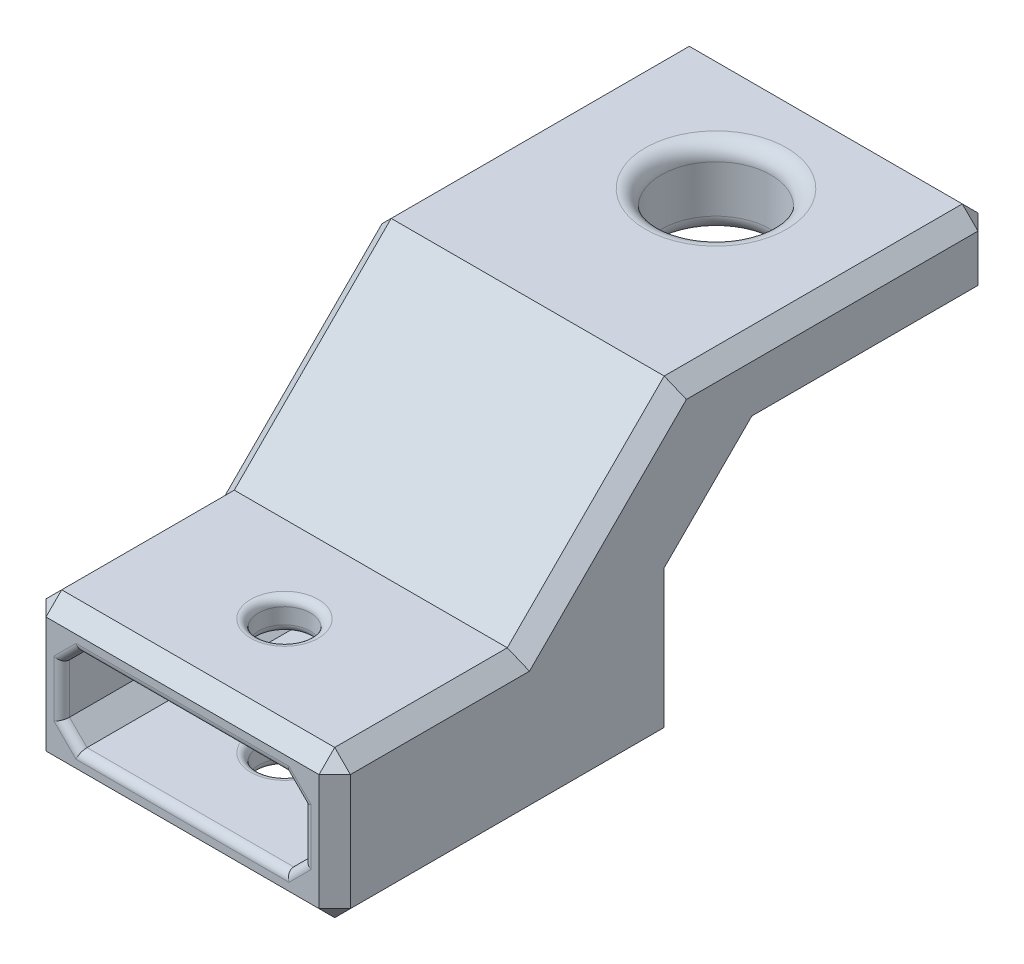
SolidWorks part; units mm, degrees
ref_plane "Plano frontal" through (0, 0, 0) normal (0, 0, 1) x (1, 0, 0)
ref_plane "Plano superior" through (0, 0, 0) normal (0, 1, 0) x (1, 0, 0)
ref_plane "Plano direito" through (0, 0, 0) normal (1, 0, 0) x (0, 0, -1)
sketch "Esboço1" plane through (0, 0, 0) normal (0, 0, 1) x (1, 0, 0)
  line L0 (15, 3) -> (14, 4) construction
  line L1 (15, 3) -> (15, 0) construction
  line L2 (14, -1) -> (15, 0) construction
  line L3 (14, -1) -> (1, -1) construction
  line L4 (0, 0) -> (1, -1) construction
  line L5 (0, 0) -> (0, 3) construction
  line L6 (1, 4) -> (0, 3) construction
  line L7 (1, 4) -> (14, 4) construction
sketch "Esboço2" plane through (0, 0, 0) normal (0, 0, 1) x (1, 0, 0)
  line L39 (-2.2, 6.2) -> (17.2, 6.2)
  line L40 (-2.2, 6.2) -> (-2.2, -3.2)
  line L41 (-2.2, -3.2) -> (17.2, -3.2)
  line L42 (17.2, 6.2) -> (17.2, -3.2)
  line L46 (15.2, 3.0828) -> (14.0828, 4.2)
  line L47 (15.2, -0.0828) -> (15.2, 3.0828)
  line L48 (14.0828, -1.2) -> (15.2, -0.0828)
  line L49 (0.9172, -1.2) -> (14.0828, -1.2)
  line L50 (-0.2, -0.0828) -> (0.9172, -1.2)
  line L51 (-0.2, 3.0828) -> (-0.2, -0.0828)
  line L52 (0.9172, 4.2) -> (-0.2, 3.0828)
  line L53 (14.0828, 4.2) -> (0.9172, 4.2)
  line L54 (15.2, 3.0828) -> (14.0828, 4.2)
  line L55 (15.2, -0.0828) -> (15.2, 3.0828)
  line L56 (14.0828, -1.2) -> (15.2, -0.0828)
  line L57 (0.9172, -1.2) -> (14.0828, -1.2)
  line L58 (-0.2, -0.0828) -> (0.9172, -1.2)
  line L59 (-0.2, 3.0828) -> (-0.2, -0.0828)
  line L60 (0.9172, 4.2) -> (-0.2, 3.0828)
  line L61 (14.0828, 4.2) -> (0.9172, 4.2)
  dimension "D2" = 2
  dimension "D3" = 2
  dimension "D4" = 2
  dimension "D5" = 2
  dimension "D1" = 0.2
extrude "Ressalto-extrusão1" add sketch "Esboço2" along normal blind 22
ref_plane "Plano1" through (-2.2, 0, 0) normal (1, 0, 0) x (0, 0, -1)
sketch "Esboço4" plane through (-2.2, 0, 0) normal (1, 0, 0) x (0, 0, -1)
  line L0 (0, 6.2) -> (5, 11.2)
  line L1 (5, 11.2) -> (20, 11.2)
  line L2 (20, 11.2) -> (20, 16.2)
  line L4 (0, 16.2) -> (-10, 6.2)
  line L5 (-22, 6.2) -> (0, 6.2) construction
  line L7 (0, 16.2) -> (20, 16.2)
  line L13 (-10, 6.2) -> (0, 6.2)
  dimension "D1" = 15
  dimension "D2" = 10
  dimension "D3" = 135
  dimension "D4" = 5
  dimension "D5" = 135
  dimension "D6" = 5
extrude "Ressalto-extrusão2" add sketch "Esboço4" along normal up to surface (19.4 mm away) contours L4 L13 L0 L1 L2 L7 region at (-2.2, 12.0974, -5.2564) up to face at (17.2, 1.5, 11)
chamfer "Chanfro2" distance 1 angle 45 23 edges at (-2.2, 13.7, -20) (7.5, 11.2, -20) (17.2, 13.7, -20) (7.5, 16.2, -20) (-2.2, 11.2, -12.5) (-2.2, 8.7, -2.5) (17.2, 11.2, -12.5) (17.2, 8.7, -2.5) (-2.2, 16.2, -10) (-2.2, 11.2, 5) (17.2, 16.2, -10) (17.2, 11.2, 5) (7.5, -3.2, 0) (-2.2, 1.5, 0) (-2.2, -3.2, 11) (-2.2, 1.5, 22) (7.5, -3.2, 22) (17.2, 1.5, 0) (17.2, -3.2, 11) (17.2, 1.5, 22) (-2.2, 6.2, 16) (7.5, 6.2, 22) (17.2, 6.2, 16)
sketch "Esboço5" plane through (0, 11.2, 0) normal (0, -1, 0) x (1, 0, 0)
  line L0 (-1.2, -19) -> (16.2, -5) construction
  circle A0 centre (7.5, -12) radius 3.5
  dimension "D1" = 7
extrude "Corte-extrusão1" cut sketch "Esboço5" against normal blind 20 contours A0
fillet "Filete1" radius 1 2 edges at (7.5, 11.2, -15.5) (7.5, 16.2, -8.5)
fillet "Filete2" radius 0.5 16 edges at (14.6414, -0.6414, 22) (14.6414, 3.6414, 22) (15.2, 1.5, 22) (7.5, -1.2, 22) (0.3586, -0.6414, 22) (-0.2, 1.5, 22) (0.3586, 3.6414, 22) (7.5, 4.2, 22) (0.3586, 3.6414, 0) (-0.2, 1.5, 0) (0.3586, -0.6414, 0) (7.5, -1.2, 0) (14.6414, -0.6414, 0) (15.2, 1.5, 0) (14.6414, 3.6414, 0) (7.5, 4.2, 0)
sketch "Esboço6" plane through (0, 6.2, 0) normal (0, 1, 0) x (1, 0, 0)
  line L0 (7.5, -21) -> (7.5, -10) construction
  line L1 (-1.2, -21) -> (16.2, -21) construction
  line L2 (16.2, -10) -> (-1.2, -10) construction
  circle A0 centre (7.5, -15.5) radius 1.65
  dimension "D1" = 3.3
extrude "Corte-extrusão2" cut sketch "Esboço6" against normal blind 10
fillet "Filete3" radius 0.5 4 edges at (7.5, -3.2, 17.15) (7.5, -1.2, 17.15) (7.5, 6.2, 17.15) (7.5, 4.2, 13.85)
